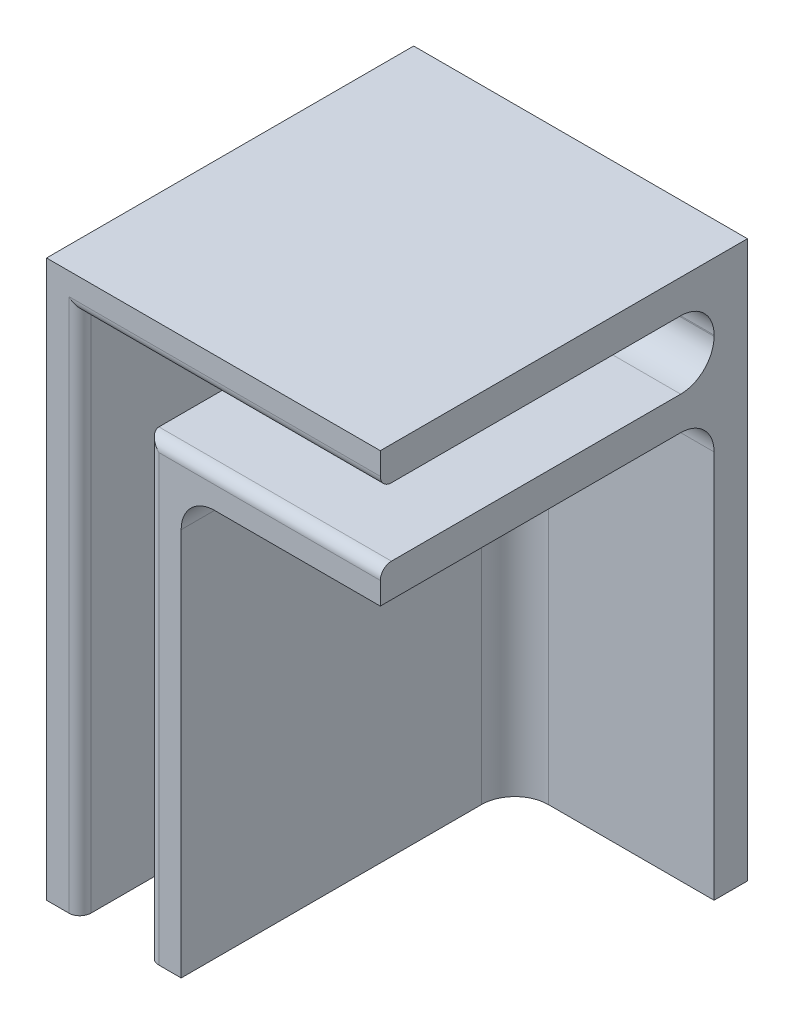
SolidWorks part; units mm, degrees
ref_plane "Front" through (0, 0, 0) normal (0, 0, 1) x (1, 0, 0)
ref_plane "Top" through (0, 0, 0) normal (0, 1, 0) x (1, 0, 0)
ref_plane "Right" through (0, 0, 0) normal (1, 0, 0) x (0, 0, -1)
sketch "Sketch1" plane through (0, 0, 0) normal (0, 0, 1) x (1, 0, 0)
  line L5 (0, 0) -> (30, 0)
  line L6 (0, 0) -> (0, 50)
  line L7 (0, 50) -> (30, 50)
  line L8 (30, 0) -> (30, 50)
  dimension "D1" = 50
  dimension "D2" = 30
extrude "Boss-Extrude1" add sketch "Sketch1" along normal blind 3
sketch "Sketch2" plane through (0, 0, 3) normal (0, 0, 1) x (1, 0, 0)
  line L0 (30, 40.9) -> (9.1, 40.9)
  line L5 (30, 0) -> (30, 50) construction
  line L10 (9.1, 40.9) -> (9.1, 0)
  line L15 (0, 50) -> (30, 50)
  line L16 (0, 50) -> (0, 49)
  line L17 (3, 47) -> (30, 47)
  line L18 (30, 50) -> (30, 47)
  line L19 (0, 0) -> (30, 0) construction
  line L21 (0, 49) -> (0, 0)
  line L22 (0, 0) -> (3, 0)
  line L23 (3, 47) -> (3, 0)
  line L24 (9.1, 0) -> (12.1, 0)
  line L25 (30, 37.9) -> (12.1, 37.9)
  line L26 (30, 37.9) -> (30, 40.9)
  line L32 (12.1, 37.9) -> (12.1, 0)
  dimension "D1" = 3
  dimension "D2" = 6.1
  dimension "D3" = 6.1
extrude "Boss-Extrude2" add sketch "Sketch2" along normal blind 30
fillet "Fillet1" radius 3 7 edges at (19.55, 40.9, 3) (16.5, 47, 3) (12.1, 37.9, 18) (21.05, 37.9, 3) (12.1, 18.95, 3) (9.1, 20.45, 3) (3, 23.5, 3)
fillet "Fillet2" radius 1 4 edges at (3, 23.5, 33) (16.5, 47, 33) (19.55, 40.9, 33) (9.1, 20.45, 33)
